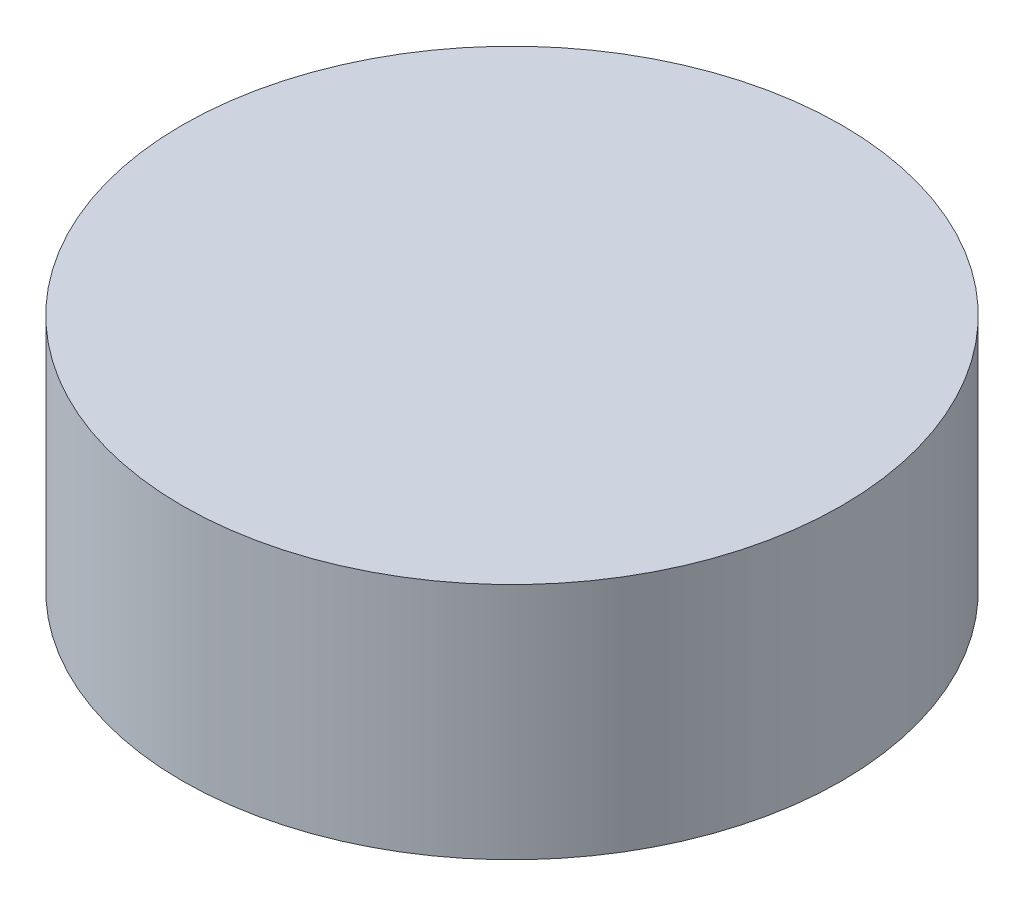
SolidWorks part; units mm, degrees
ref_plane "Front Plane" through (0, 0, 0) normal (0, 0, 1) x (1, 0, 0)
ref_plane "Top Plane" through (0, 0, 0) normal (0, 1, 0) x (1, 0, 0)
ref_plane "Right Plane" through (0, 0, 0) normal (1, 0, 0) x (0, 0, -1)
sketch "Sketch2" plane through (0, 14, 0) normal (0, 1, 0) x (1, 0, 0)
  line L0 (0, 0) -> (-0.498, 0)
  circle A2 centre (-0.498, 0) radius 12.45
  dimension "D1" = 24.9
extrude "Boss-Extrude2" add sketch "Sketch2" along normal blind 2 and the other way blind 7 contours A2
sketch "Sketch3" plane through (0, 7, 0) normal (0, -1, 0) x (1, 0, 0)
  line L0 (0, 0) -> (-0.5, 0) construction
  circle A0 centre (-0.5, 0) radius 10
  circle A1 centre (9.5, 0) radius 1.475
  circle A2 centre (4.5, -8.6603) radius 1.475
  circle A3 centre (-5.5, -8.6603) radius 1.475
  circle A4 centre (-10.5, 0) radius 1.475
  circle A5 centre (-5.5, 8.6603) radius 1.475
  circle A6 centre (4.5, 8.6603) radius 1.475
  dimension "D1" = 2.95
  dimension "D2" = 6
extrude "Cut-Extrude1" cut sketch "Sketch3" against normal blind 6.05 contours A1 | A6 | A5 | A4 | A3 | A2
